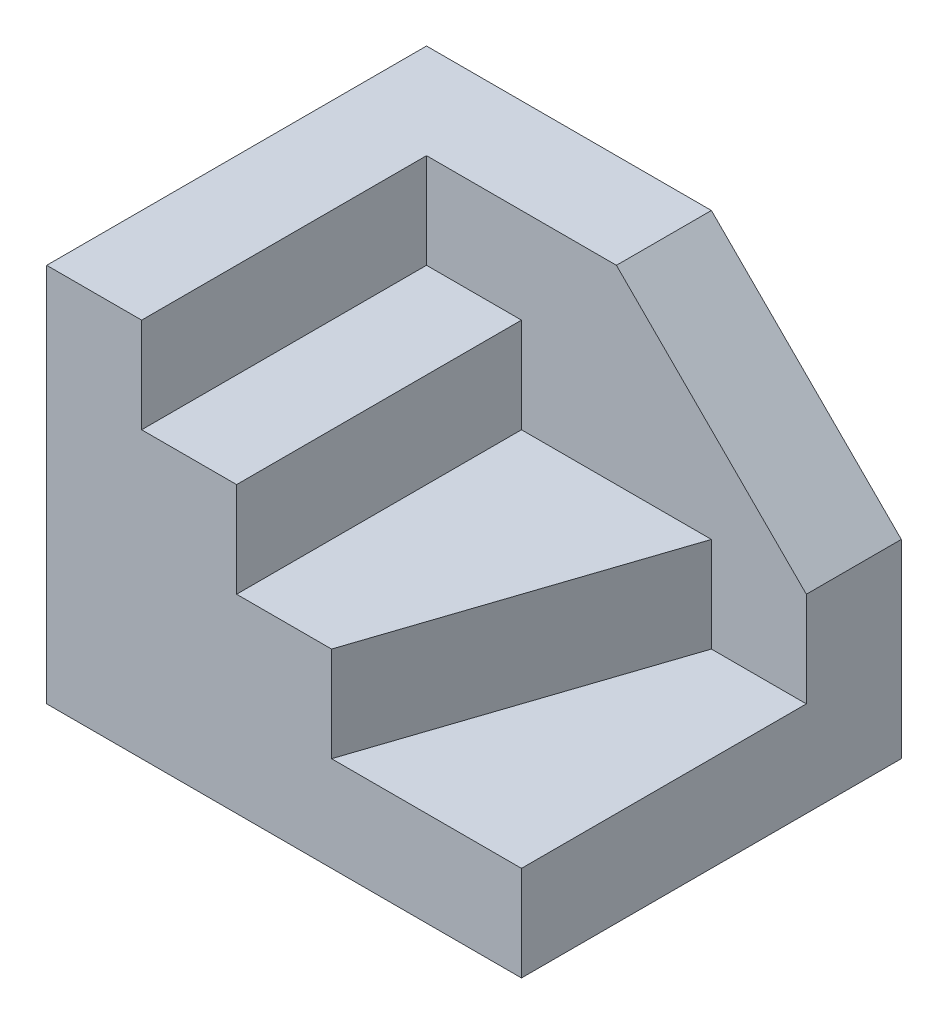
SolidWorks part; units mm, degrees
ref_plane "前基準面" through (0, 0, 0) normal (0, 0, 1) x (1, 0, 0)
ref_plane "上基準面" through (0, 0, 0) normal (0, 1, 0) x (1, 0, 0)
ref_plane "右基準面" through (0, 0, 0) normal (1, 0, 0) x (0, 0, -1)
sketch "草圖1" plane through (0, 0, 0) normal (0, 1, 0) x (1, 0, 0)
  line L0 (2.5, 1) -> (-1.5, 1)
  line L1 (2.5, -2) -> (-2.5, -2)
  line L2 (2.5, -2) -> (2.5, 2)
  line L3 (2.5, 2) -> (-2.5, 2)
  line L4 (-2.5, -2) -> (-2.5, 2)
  line L5 (2.5, -2) -> (-2.5, 2) construction
  line L6 (2.5, 2) -> (-2.5, -2) construction
  line L7 (-1.5, 1) -> (-1.5, -2)
  line L8 (-1.5, -2) -> (-0.5, -2)
  line L9 (-0.5, -2) -> (-0.5, 1)
  line L10 (-0.5, 1) -> (1.5, 1)
  line L11 (1.5, 1) -> (0.5, -2)
  point P0 (0, 0)
  dimension "D1" = 4
  dimension "D2" = 5
  dimension "D3" = 1
  dimension "D4" = 1
  dimension "D5" = 1
  dimension "D6" = 1
  dimension "D7" = 2
extrude "填料-伸長1" add sketch "草圖1" along normal blind 1 contours L7 L0 L2 L3 L4 L1 | L1 L9 L0 L7 | L11 L0 L9 L1 | L0 L11 L1 L2 region at (1.7222, 0, 0.6667) region at (2, 0, -1.064) region at (0.2778, 0, 0.3333) region at (-1, 0, 0.5)
extrude "填料-伸長2" add sketch "草圖1<3>" along normal blind 2 contours L11 L0 L9 L1 region at (0.2778, 0, 0.3333)
sketch "草圖1<3>" plane through (0, 0, 0) normal (0, 1, 0) x (1, 0, 0) same geometry as "草圖1"
extrude "填料-伸長3" add sketch "草圖1<4>" along normal blind 3 contours L1 L9 L0 L7 region at (-1, 0, 0.5)
sketch "草圖1<4>" plane through (0, 0, 0) normal (0, 1, 0) x (1, 0, 0) same geometry as "草圖1"
extrude "填料-伸長4" add sketch "草圖1<5>" along normal blind 4 contours L7 L0 L2 L3 L4 L1 region at (2, 0, -1.064)
sketch "草圖1<5>" plane through (0, 0, 0) normal (0, 1, 0) x (1, 0, 0) same geometry as "草圖1"
sketch "草圖2" plane through (0, 0, -1) normal (0, 0, 1) x (1, 0, 0)
  line L0 (2.5, 4) -> (0.5, 4)
  line L1 (2.5, 4) -> (-1.5, 4) construction
  line L2 (0.5, 4) -> (2.5, 2)
  line L3 (2.5, 4) -> (2.5, 1) construction
  line L4 (2.5, 2) -> (2.5, 4)
  dimension "D1" = 2
  dimension "D2" = 2
extrude "除料-伸長1" cut sketch "草圖2" against normal blind 4
